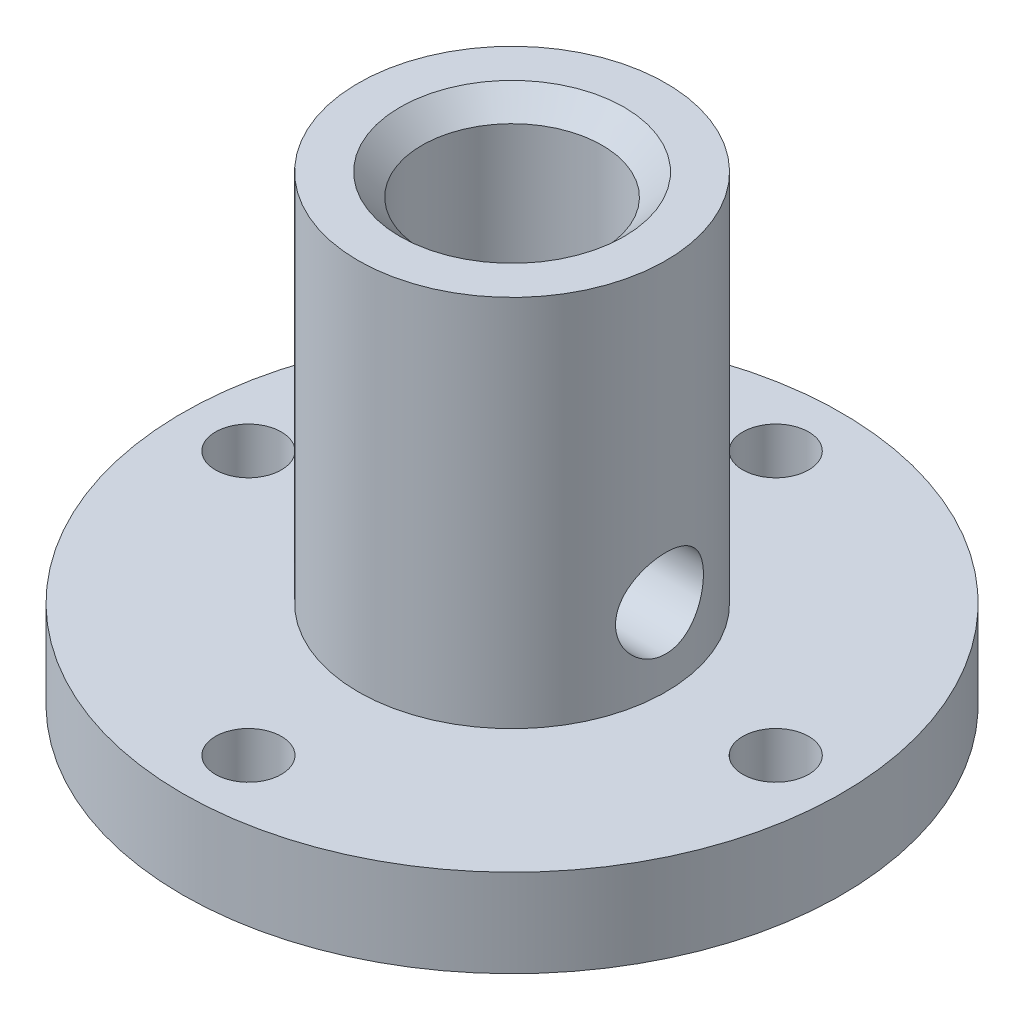
SolidWorks part; units mm, degrees
ref_plane "前视基准面" through (0, 0, 0) normal (0, 0, 1) x (1, 0, 0)
ref_plane "上视基准面" through (0, 0, 0) normal (0, 1, 0) x (1, 0, 0)
ref_plane "右视基准面" through (0, 0, 0) normal (1, 0, 0) x (0, 0, -1)
sketch "草图1" plane through (0, 0, 0) normal (0, 1, 0) x (1, 0, 0)
  circle A0 centre (0, 0) radius 15
  circle A1 centre (0, 0) radius 4.1
  dimension "D1" = 30
  dimension "D2" = 8.2
extrude "凸台-拉伸1" add sketch "草图1" along normal blind 4 contours A1 | A0 region at (0, 0, 0)
sketch "草图2" plane through (0, 4, 0) normal (0, 1, 0) x (1, 0, 0)
  circle A0 centre (0, 0) radius 4.1
  circle A1 centre (0, 0) radius 7
  dimension "D1" = 14
  dimension "D2" = 8.2
extrude "凸台-拉伸2" add sketch "草图2" along normal blind 17
ref_axis "基准轴1" through (0, 21, 0) along (0, -1, 0)
sketch "草图4" plane through (0, 0, 0) normal (0, -1, 0) x (-1, 0, 0)
  line L0 (0, 0) -> (0, -10.4165)
ref_plane "基准面1" through (0, 0, 0) normal (-1, 0, 0) x (0, 0, 1)
sketch "草图5" plane through (0, 0, 0) normal (-1, 0, 0) x (0, 0, 1)
  line L0 (7, 21) -> (-7, 21) construction
  line L1 (-7, 21) -> (-7, 4) construction
  circle A0 centre (0, 7.5) radius 2
  dimension "D1" = 4
  dimension "D2" = 13.5
  dimension "D3" = 7
extrude "切除-拉伸1" cut sketch "草图5" against normal blind 12
sketch "草图6" plane through (0, 0, 0) normal (0, -1, 0) x (1, 0, 0)
  circle A0 centre (0, 0) radius 4
  dimension "D1" = 8
sketch "草图7" plane through (0, 4, 0) normal (0, 1, 0) x (1, 0, 0)
  circle A0 centre (0, -12) radius 1.5
  circle A1 centre (-12, 0) radius 1.5
  circle A2 centre (0, 12) radius 1.5
  circle A3 centre (12, 0) radius 1.5
  point P12 (0, 0)
  dimension "D1" = 0
  dimension "D2" = 12
  dimension "D3" = 3
  dimension "D4" = 4
extrude "切除-拉伸3" cut sketch "草图7" against normal blind 4 contours A3 | A0 | A1 | A2 region at (12, 4, 0)
chamfer "倒角1" distance 1 angle 45 1 edges at (0, 21, 4.1)
